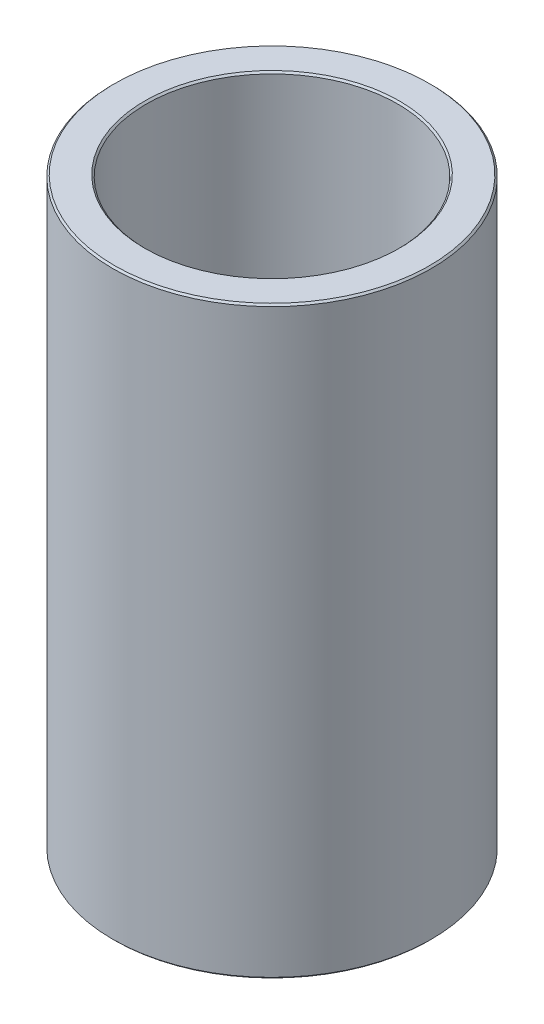
SolidWorks part; units mm, degrees
ref_plane "Front Plane" through (0, 0, 0) normal (0, 0, 1) x (1, 0, 0)
ref_plane "Top Plane" through (0, 0, 0) normal (0, 1, 0) x (1, 0, 0)
ref_plane "Right Plane" through (0, 0, 0) normal (1, 0, 0) x (0, 0, -1)
sketch "Sketch1" plane through (0, 0, 0) normal (0, 1, 0) x (1, 0, 0)
  circle A0 centre (0, 0) radius 50
  dimension "SLEEVE_OD" = 100
extrude "Boss-Extrude1" add sketch "Sketch1" along normal blind 183.3946
sketch "Sketch2" plane through (0, 0, 0) normal (0, 1, 0) x (1, 0, 0)
  circle A0 centre (0, 0) radius 39.4783
  dimension "BORE_D" = 78.9566
extrude "Cut-Extrude1" cut sketch "Sketch2" along normal through all
chamfer "Chamfer1" distance 0.5419 angle 45 4 edges at (0, 183.3946, 39.4783) (0, 0, 39.4783) (0, 0, 50) (0, 183.3946, 50)
